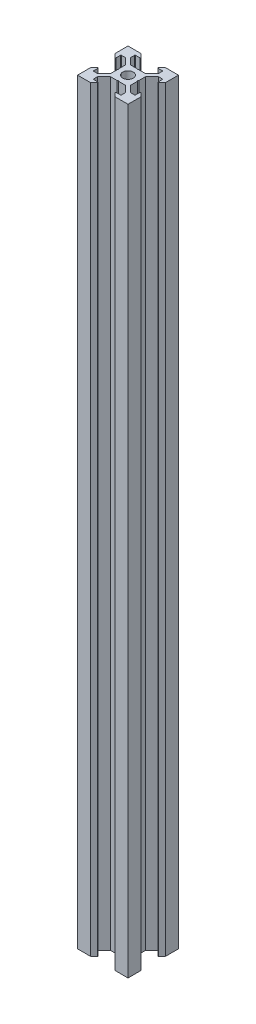
SolidWorks part; units mm, degrees
ref_plane "Plan de face" through (0, 0, 0) normal (0, 0, 1) x (1, 0, 0)
ref_plane "Plan de dessus" through (0, 0, 0) normal (0, 1, 0) x (1, 0, 0)
ref_plane "Plan de droite" through (0, 0, 0) normal (1, 0, 0) x (0, 0, -1)
sketch "Esquisse1" plane through (0, 0, 0) normal (0, 0, 1) x (1, 0, 0)
  line L1 (-10, -150) -> (10, -150)
  line L2 (-10, -150) -> (-10, 150)
  line L3 (-10, 150) -> (10, 150)
  line L4 (10, -150) -> (10, 150)
  line L5 (-10, -150) -> (10, 150) construction
  line L6 (-10, 150) -> (10, -150) construction
  point P0 (0, 0)
  dimension "D1" = 20
  dimension "D2" = 300
extrude "Boss.-Extru.1" add sketch "Esquisse1" along normal blind 10 and the other way blind 10
sketch "Esquisse2" plane through (0, 150, 0) normal (0, 1, 0) x (1, 0, 0)
  line L0 (0, 10) -> (0, -10) construction
  line L1 (-10, -10) -> (10, -10)
  line L2 (-10, -10) -> (-10, 10)
  line L3 (-10, 10) -> (10, 10)
  line L4 (10, -10) -> (10, 10)
  line L5 (-10, -10) -> (10, 10) construction
  line L6 (-10, 10) -> (10, -10) construction
  line L7 (-10, 0) -> (10, 0) construction
  line L8 (-4.8, 10) -> (-3.4414, 8.6414)
  line L9 (-10, 5.5) -> (10, 5.5) construction
  line L10 (-5.5, -10) -> (-5.5, 10) construction
  line L11 (5.5, -10) -> (5.5, 10) construction
  line L12 (-10, -5.5) -> (10, -5.5) construction
  line L13 (-3.1, -8.3) -> (-3.1, -10) construction
  line L14 (3.1, -8.3) -> (3.1, -10) construction
  line L15 (-10, -8.3) -> (10, -8.3) construction
  line L16 (-8.3, 10) -> (-8.3, -10) construction
  line L17 (2.9393, -4) -> (-2.9393, -4)
  line L18 (4, -2.9393) -> (4, 2.9393)
  line L19 (2.9393, 4) -> (-2.9393, 4)
  line L20 (-4, -2.9393) -> (-4, 2.9393)
  line L21 (4, -4) -> (-4, 4) construction
  line L22 (4, 4) -> (-4, -4) construction
  line L23 (-3.4414, -8.6414) -> (-4.8, -10)
  line L24 (-3.5828, 8.3) -> (-5.3, 8.3)
  line L25 (-10, -4.8) -> (-8.6414, -3.4414)
  line L26 (-8.3, -3.5828) -> (-8.3, -5.3)
  line L27 (-3.5828, -8.3) -> (-5.3, -8.3)
  line L28 (-8.1, -5.5) -> (-6.5607, -5.5)
  line L29 (-5.5, -6.5607) -> (-5.5, -8.1)
  line L30 (-5.5, -6.5607) -> (-2.9393, -4)
  line L31 (-6.5607, -5.5) -> (-4, -2.9393)
  line L32 (-5.5, 8.1) -> (-5.5, 6.5607)
  line L33 (-10.5303, -9.4697) -> (9.4697, 10.5303) construction
  line L34 (-9.4697, -10.5303) -> (10.5303, 9.4697) construction
  line L35 (-5.5, 6.5607) -> (-2.9393, 4)
  line L36 (-6.5607, 5.5) -> (-4, 2.9393)
  line L37 (-6.5607, 5.5) -> (-8.1, 5.5)
  line L38 (-8.3, 3.5828) -> (-8.3, 5.3)
  line L39 (-8.6414, 3.4414) -> (-10, 4.8)
  line L40 (10, 4.8) -> (8.6414, 3.4414)
  line L41 (8.3, 3.5828) -> (8.3, 5.3)
  line L42 (8.1, 5.5) -> (6.5607, 5.5)
  line L43 (6.5607, 5.5) -> (4, 2.9393)
  line L44 (5.5, 6.5607) -> (2.9393, 4)
  line L45 (5.5, 6.5607) -> (5.5, 8.1)
  line L46 (3.5828, 8.3) -> (5.3, 8.3)
  line L47 (3.4414, 8.6414) -> (4.8, 10)
  line L48 (4.8, -10) -> (3.4414, -8.6414)
  line L49 (3.5828, -8.3) -> (5.3, -8.3)
  line L50 (5.5, -8.1) -> (5.5, -6.5607)
  line L51 (5.5, -6.5607) -> (2.9393, -4)
  line L52 (6.5607, -5.5) -> (4, -2.9393)
  line L53 (6.5607, -5.5) -> (8.1, -5.5)
  line L54 (8.3, -3.5828) -> (8.3, -5.3)
  line L55 (8.6414, -3.4414) -> (10, -4.8)
  line L56 (-4, 0.2828) -> (-3.7172, 0)
  line L57 (-3.7172, 0) -> (-4, -0.2828)
  line L58 (0.2828, 4) -> (0, 3.7172)
  line L59 (0, 3.7172) -> (-0.2828, 4)
  line L60 (4, -0.2828) -> (3.7172, 0)
  line L61 (3.7172, 0) -> (4, 0.2828)
  line L62 (-0.2828, -4) -> (0, -3.7172)
  line L63 (0, -3.7172) -> (0.2828, -4)
  circle A0 centre (0, 0) radius 2.1
  arc A1 (-8.3, -3.5828) -> (-8.6414, -3.4414) centre (-8.5, -3.5828) ccw
  arc A2 (-3.5828, -8.3) -> (-3.4414, -8.6414) centre (-3.5828, -8.5) cw
  arc A3 (8.3, -3.5828) -> (8.6414, -3.4414) centre (8.5, -3.5828) cw
  arc A4 (8.6414, 3.4414) -> (8.3, 3.5828) centre (8.5, 3.5828) cw
  arc A5 (3.5828, 8.3) -> (3.4414, 8.6414) centre (3.5828, 8.5) cw
  arc A6 (-3.4414, 8.6414) -> (-3.5828, 8.3) centre (-3.5828, 8.5) cw
  arc A7 (-8.3, 3.5828) -> (-8.6414, 3.4414) centre (-8.5, 3.5828) cw
  arc A8 (-8.1, 5.5) -> (-8.3, 5.3) centre (-8.1, 5.3) ccw
  arc A9 (-5.3, 8.3) -> (-5.5, 8.1) centre (-5.3, 8.1) ccw
  arc A10 (5.5, 8.1) -> (5.3, 8.3) centre (5.3, 8.1) ccw
  arc A11 (8.3, 5.3) -> (8.1, 5.5) centre (8.1, 5.3) ccw
  arc A12 (8.1, -5.5) -> (8.3, -5.3) centre (8.1, -5.3) ccw
  arc A13 (5.3, -8.3) -> (5.5, -8.1) centre (5.3, -8.1) ccw
  arc A14 (-5.3, -8.3) -> (-5.5, -8.1) centre (-5.3, -8.1) cw
  arc A15 (-8.3, -5.3) -> (-8.1, -5.5) centre (-8.1, -5.3) ccw
  arc A16 (3.4414, -8.6414) -> (3.5828, -8.3) centre (3.5828, -8.5) cw
  point P0 (0, 0)
  point P16 (0, -8.3)
  point P19 (0, -4.9968)
  point P81 (-8.3, -3.1)
  point P109 (-5.5, -8.3)
  dimension "D1" = 4.2
  dimension "D15" = 0.2
  dimension "D2" = 0.2
  dimension "D3" = 11
  dimension "D4" = 4.5
  dimension "D5" = 4.5
  dimension "D6" = 11
  dimension "D7" = 6
  dimension "D8" = 4.3
  dimension "D9" = 4.3
  dimension "D10" = 45
  dimension "D11" = 45
  dimension "D17" = 0.4
  dimension "D16" = 0.4
  dimension "D12" = 0.75
  dimension "D13" = 0.75
  dimension "D14" = 4
  dimension "D18" = 4
extrude "Enlèv. mat.-Extru.1" cut sketch "Esquisse2" against normal through all contours A0 | L46 L47 L3 L8 L24 L32 L35 L19 L44 L45 | L38 L39 L2 L25 L26 L28 L31 L20 L36 L37 | L54 L55 L4 L40 L41 L42 L43 L18 L52 L53 | L50 L51 L17 L30 L29 L27 L23 L1 L48 L49 | L57 L56 L20 | L59 L58 L19 | L61 L60 L18 | L63 L62 L17 region at (0, 150, 7.0678) region at (-7.0678, 150, 0) region at (7.0678, 150, 0) region at (0, 150, -7.0678) region at (0, 150, 3.9057) region at (-3.9057, 150, 0) region at (3.9057, 150, 0) region at (0, 150, -3.9057) region at (0, 150, 0)
equation "\"D5@Esquisse2\"=\"D4@Esquisse2\""
equation "\"D6@Esquisse2\"=\"D3@Esquisse2\""
equation "\"D16@Esquisse2\"=\"D17@Esquisse2\""
